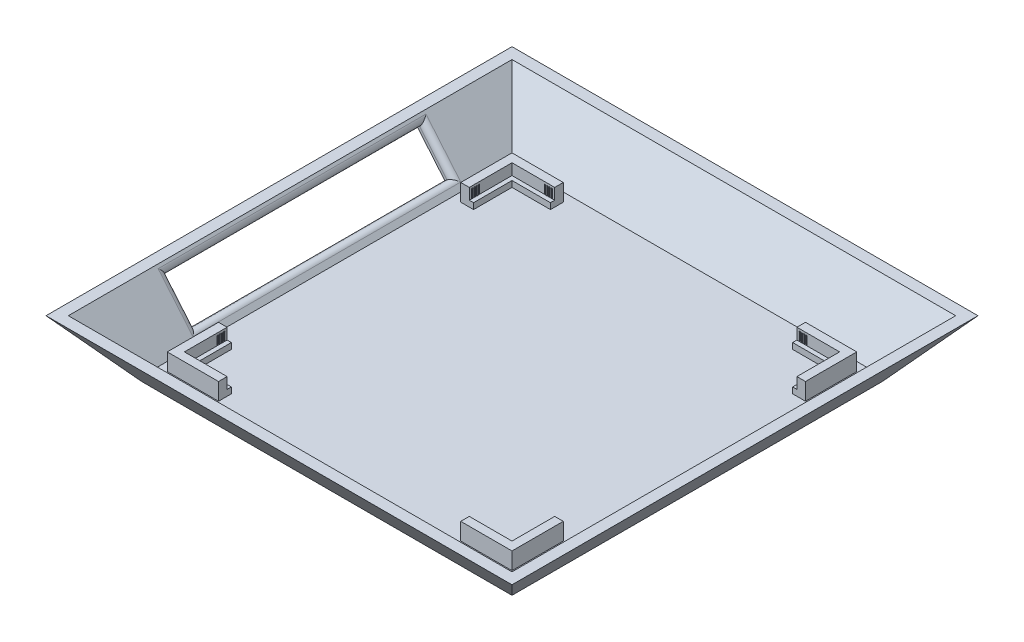
SolidWorks part; units mm, degrees
ref_plane "Front Plane" through (0, 0, 0) normal (0, 0, 1) x (1, 0, 0)
ref_plane "Top Plane" through (0, 0, 0) normal (0, 1, 0) x (1, 0, 0)
ref_plane "Right Plane" through (0, 0, 0) normal (1, 0, 0) x (0, 0, -1)
sketch "Sketch1" plane through (0, 0, 0) normal (0, 1, 0) x (1, 0, 0)
  line L1 (-65, -65) -> (65, -65)
  line L2 (-65, -65) -> (-65, 65)
  line L3 (-65, 65) -> (65, 65)
  line L4 (65, -65) -> (65, 65)
  line L5 (-65, -65) -> (65, 65) construction
  line L6 (-65, 65) -> (65, -65) construction
  point P0 (0, 0)
  dimension "D1" = 130
  dimension "D2" = 130
extrude "Boss-Extrude1" add sketch "Sketch1" along normal blind 20 draft 40 draft outward yes
shell "Shell1" thickness 3 removed face at (0, 20, 0)
sketch "Sketch2" plane through (0, 3, 0) normal (0, 1, 0) x (1, 0, 0)
  line L1 (-57.5, -57.5) -> (57.5, -57.5)
  line L2 (-57.5, -57.5) -> (-57.5, 57.5)
  line L3 (-57.5, 57.5) -> (57.5, 57.5)
  line L4 (57.5, -57.5) -> (57.5, 57.5)
  line L5 (-57.5, -57.5) -> (57.5, 57.5) construction
  line L6 (-57.5, 57.5) -> (57.5, -57.5) construction
  line L7 (57.5, 57.5) -> (42.5, 57.5)
  line L8 (57.5, 57.5) -> (57.5, 42.5)
  line L9 (57.5, 42.5) -> (42.5, 42.5)
  line L10 (42.5, 57.5) -> (42.5, 42.5)
  line L11 (-57.5, 57.5) -> (-42.5, 57.5)
  line L12 (-57.5, 57.5) -> (-57.5, 42.5)
  line L13 (-57.5, 42.5) -> (-42.5, 42.5)
  line L14 (-42.5, 57.5) -> (-42.5, 42.5)
  line L15 (-57.5, -57.5) -> (-42.5, -57.5)
  line L16 (-57.5, -57.5) -> (-57.5, -42.5)
  line L17 (-57.5, -42.5) -> (-42.5, -42.5)
  line L18 (-42.5, -57.5) -> (-42.5, -42.5)
  line L19 (57.5, -57.5) -> (42.5, -57.5)
  line L20 (57.5, -57.5) -> (57.5, -42.5)
  line L21 (57.5, -42.5) -> (42.5, -42.5)
  line L22 (42.5, -57.5) -> (42.5, -42.5)
  line L23 (42.5, -57.5) -> (57.5, -57.5)
  line L24 (42.5, -57.5) -> (42.5, -60.5)
  line L25 (42.5, -60.5) -> (57.5, -60.5)
  line L26 (57.5, -57.5) -> (57.5, -60.5)
  line L27 (57.5, -42.5) -> (60.5, -42.5)
  line L28 (57.5, -42.5) -> (57.5, -60.5)
  line L29 (57.5, -60.5) -> (60.5, -60.5)
  line L30 (60.5, -42.5) -> (60.5, -60.5)
  line L31 (-57.5, -57.5) -> (-42.5, -57.5)
  line L32 (-57.5, -57.5) -> (-57.5, -60.5)
  line L33 (-57.5, -60.5) -> (-42.5, -60.5)
  line L34 (-42.5, -57.5) -> (-42.5, -60.5)
  line L35 (-57.5, -42.5) -> (-60.5, -42.5)
  line L36 (-57.5, -42.5) -> (-57.5, -60.5)
  line L37 (-57.5, -60.5) -> (-60.5, -60.5)
  line L38 (-60.5, -42.5) -> (-60.5, -60.5)
  line L39 (42.5, 57.5) -> (57.5, 57.5)
  line L40 (42.5, 57.5) -> (42.5, 60.5)
  line L41 (42.5, 60.5) -> (57.5, 60.5)
  line L42 (57.5, 57.5) -> (57.5, 60.5)
  line L43 (57.5, 42.5) -> (60.5, 42.5)
  line L44 (57.5, 42.5) -> (57.5, 60.5)
  line L45 (57.5, 60.5) -> (60.5, 60.5)
  line L46 (60.5, 42.5) -> (60.5, 60.5)
  line L47 (-57.5, 57.5) -> (-42.5, 57.5)
  line L48 (-57.5, 57.5) -> (-57.5, 60.5)
  line L49 (-57.5, 60.5) -> (-42.5, 60.5)
  line L50 (-42.5, 57.5) -> (-42.5, 60.5)
  line L51 (-57.5, 42.5) -> (-60.5, 42.5)
  line L52 (-57.5, 42.5) -> (-57.5, 60.5)
  line L53 (-57.5, 60.5) -> (-60.5, 60.5)
  line L54 (-60.5, 42.5) -> (-60.5, 60.5)
  point P0 (0, 0)
  dimension "D1" = 115
  dimension "D2" = 115
  dimension "D3" = 15
  dimension "D4" = 15
  dimension "D5" = 15
  dimension "D6" = 15
  dimension "D7" = 3
  dimension "D8" = 3
  dimension "D9" = 3
  dimension "D10" = 3
  dimension "D11" = 3
  dimension "D12" = 3
  dimension "D13" = 3
  dimension "D14" = 3
extrude "Boss-Extrude2" add sketch "Sketch2" along normal blind 6 contours L54 L51 L2 L48 L53 | L3 L50 L49 L48 | L35 L38 L37 L32 L2 | L3 L42 L41 L40 | L43 L46 L45 L42 L4 | L34 L1 L32 L33 | L26 L1 L24 L25 | L30 L27 L4 L26 L29 region at (-59, 3, 51.5) region at (-50, 3, 59) region at (50, 3, 59) region at (-59, 3, -51.5) region at (59, 3, 51.5) region at (-50, 3, -59) region at (59, 3, -51.5) region at (50, 3, -59)
sketch "Sketch3" plane through (0, 3, 0) normal (0, 1, 0) x (1, 0, 0)
  line L1 (-57.5, -57.5) -> (57.5, -57.5)
  line L2 (-57.5, -57.5) -> (-57.5, 57.5)
  line L3 (-57.5, 57.5) -> (57.5, 57.5)
  line L4 (57.5, -57.5) -> (57.5, 57.5)
  line L5 (-57.5, -57.5) -> (57.5, 57.5) construction
  line L6 (-57.5, 57.5) -> (57.5, -57.5) construction
  line L7 (-57.5, 42.5) -> (-56, 42.5)
  line L8 (-57.5, 42.5) -> (-57.5, 57.5)
  line L9 (-57.5, 57.5) -> (-56, 57.5)
  line L10 (-56, 42.5) -> (-56, 57.5)
  line L11 (-42.5, 57.5) -> (-56, 57.5)
  line L12 (-42.5, 57.5) -> (-42.5, 56)
  line L13 (-42.5, 56) -> (-56, 56)
  line L14 (-56, 57.5) -> (-56, 56)
  line L15 (57.5, 42.5) -> (56, 42.5)
  line L16 (57.5, 42.5) -> (57.5, 57.5)
  line L17 (57.5, 57.5) -> (56, 57.5)
  line L18 (56, 42.5) -> (56, 57.5)
  line L19 (42.5, 57.5) -> (56, 57.5)
  line L20 (42.5, 57.5) -> (42.5, 56)
  line L21 (42.5, 56) -> (56, 56)
  line L22 (56, 57.5) -> (56, 56)
  line L23 (-57.5, -42.5) -> (-56, -42.5)
  line L24 (-57.5, -42.5) -> (-57.5, -57.5)
  line L25 (-57.5, -57.5) -> (-56, -57.5)
  line L26 (-56, -42.5) -> (-56, -57.5)
  line L27 (-42.5, -57.5) -> (-56, -57.5)
  line L28 (-42.5, -57.5) -> (-42.5, -56)
  line L29 (-42.5, -56) -> (-56, -56)
  line L30 (-56, -57.5) -> (-56, -56)
  line L31 (57.5, -42.5) -> (56, -42.5)
  line L32 (57.5, -42.5) -> (57.5, -57.5)
  line L33 (57.5, -57.5) -> (56, -57.5)
  line L34 (56, -42.5) -> (56, -57.5)
  line L35 (42.5, -57.5) -> (56, -57.5)
  line L36 (42.5, -57.5) -> (42.5, -56)
  line L37 (42.5, -56) -> (56, -56)
  line L38 (56, -57.5) -> (56, -56)
  point P0 (0, 0)
  line M10 (-57.5, -42.5) -> (-57.5, -57.5)
  line M11 (-57.5, -57.5) -> (-42.5, -57.5)
  line M24 (-57.5, 57.5) -> (-57.5, 42.5)
  line M25 (57.5, 57.5) -> (42.5, 57.5)
  line M30 (57.5, 42.5) -> (57.5, 57.5)
  line M33 (42.5, -57.5) -> (57.5, -57.5)
  line M34 (57.5, -57.5) -> (57.5, -42.5)
  dimension "D1" = 1.5
  dimension "D2" = 1.5
  dimension "D3" = 1.5
  dimension "D4" = 1.5
extrude "Boss-Extrude3" add sketch "Sketch3" along normal blind 2.1 contours L7 L10 L3 M24 | L20 L21 L18 L3 | L18 L15 M30 M25 | L26 L23 M10 M11 | L28 L29 L26 L1 | L37 L36 L34 M33 | L31 L34 L1 M34 | L11 L12 L13 L14 region at (-56.75, 3, 50) region at (-49.25, 3, 56.75) region at (-56.75, 3, -50) region at (49.25, 3, 56.75) region at (56.75, 3, 50) region at (49.25, 3, -56.75) region at (56.75, 3, -50)
sketch "Sketch4" plane through (0, 0, -57.5) normal (0, 0, 1) x (1, 0, 0)
  line L1 (-43.3, 8.25) -> (-43.7, 8.25)
  line L2 (-43.3, 8.25) -> (-43.3, 5.25)
  line L3 (-43.3, 5.25) -> (-43.7, 5.25)
  line L4 (-43.7, 8.25) -> (-43.7, 5.25)
  line L5 (-44.1, 8.25) -> (-44.5, 8.25)
  line L6 (-44.1, 8.25) -> (-44.1, 5.25)
  line L7 (-44.1, 5.25) -> (-44.5, 5.25)
  line L8 (-44.5, 8.25) -> (-44.5, 5.25)
  line L9 (-44.9, 8.25) -> (-45.3, 8.25)
  line L10 (-44.9, 8.25) -> (-44.9, 5.25)
  line L11 (-44.9, 5.25) -> (-45.3, 5.25)
  line L12 (-45.3, 8.25) -> (-45.3, 5.25)
  line L13 (-45.7, 8.25) -> (-46.1, 8.25)
  line L14 (-45.7, 8.25) -> (-45.7, 5.25)
  line L15 (-45.7, 5.25) -> (-46.1, 5.25)
  line L16 (-46.1, 8.25) -> (-46.1, 5.25)
  line L17 (-57.5, 9) -> (-42.5, 9) construction
  line L18 (-42.5, 9) -> (-42.5, 5.1) construction
  dimension "D1" = 0.4
  dimension "D2" = 0.4
  dimension "D3" = 0.4
  dimension "D4" = 0.4
  dimension "D5" = 3
  dimension "D6" = 3
  dimension "D7" = 3
  dimension "D8" = 3
  dimension "D9" = 0.75
  dimension "D10" = 0.75
  dimension "D11" = 0.75
  dimension "D12" = 0.75
  dimension "D13" = 0.8
  dimension "D14" = 0.4
  dimension "D15" = 0.4
  dimension "D16" = 0.4
extrude "Boss-Extrude4" add sketch "Sketch4" along normal blind 0.2
chamfer "Chamfer2" distance 0.15 angle 45 8 edges at (-43.3, 6.75, -57.3) (-43.7, 6.75, -57.3) (-44.1, 6.75, -57.3) (-44.5, 6.75, -57.3) (-44.9, 6.75, -57.3) (-45.3, 6.75, -57.3) (-45.7, 6.75, -57.3) (-46.1, 6.75, -57.3)
sketch "Sketch5" plane through (-57.5, 0, 0) normal (1, 0, 0) x (0, 0, -1)
  line L0 (42.5, 9) -> (42.5, 5.1) construction
  line L1 (43.3, 8.25) -> (43.7, 8.25)
  line L2 (43.3, 8.25) -> (43.3, 5.25)
  line L3 (43.3, 5.25) -> (43.7, 5.25)
  line L4 (43.7, 8.25) -> (43.7, 5.25)
  line L5 (42.5, 9) -> (57.5, 9) construction
  line L6 (44.1, 8.25) -> (44.1, 5.25)
  line L7 (44.1, 8.25) -> (44.5, 8.25)
  line L8 (44.5, 8.25) -> (44.5, 5.25)
  line L9 (44.1, 5.25) -> (44.5, 5.25)
  line L10 (44.9, 8.25) -> (44.9, 5.25)
  line L11 (44.9, 8.25) -> (45.3, 8.25)
  line L12 (45.3, 8.25) -> (45.3, 5.25)
  line L13 (44.9, 5.25) -> (45.3, 5.25)
  line L14 (45.7, 8.25) -> (45.7, 5.25)
  line L15 (45.7, 8.25) -> (46.1, 8.25)
  line L16 (46.1, 8.25) -> (46.1, 5.25)
  line L17 (45.7, 5.25) -> (46.1, 5.25)
  dimension "D1" = 0.4
  dimension "D2" = 3
  dimension "D3" = 0.8
  dimension "D4" = 0.75
  dimension "D5" = 4
extrude "Boss-Extrude5" add sketch "Sketch5" along normal blind 0.2
chamfer "Chamfer3" distance 0.15 angle 45 8 edges at (-57.3, 6.75, -46.1) (-57.3, 6.75, -45.7) (-57.3, 6.75, -45.3) (-57.3, 6.75, -44.9) (-57.3, 6.75, -44.1) (-57.3, 6.75, -44.5) (-57.3, 6.75, -43.7) (-57.3, 6.75, -43.3)
sketch "Sketch6" plane through (-57.5, 0, 0) normal (1, 0, 0) x (0, 0, -1)
  line L0 (-42.5, 9) -> (-42.5, 5.1) construction
  line L1 (-43.3, 8.25) -> (-43.7, 8.25)
  line L2 (-43.3, 8.25) -> (-43.3, 5.25)
  line L3 (-43.3, 5.25) -> (-43.7, 5.25)
  line L4 (-43.7, 8.25) -> (-43.7, 5.25)
  line L5 (-42.5, 9) -> (-57.5, 9) construction
  line L6 (-44.1, 8.25) -> (-44.1, 5.25)
  line L7 (-44.1, 8.25) -> (-44.5, 8.25)
  line L8 (-44.5, 8.25) -> (-44.5, 5.25)
  line L9 (-44.1, 5.25) -> (-44.5, 5.25)
  line L10 (-44.9, 8.25) -> (-44.9, 5.25)
  line L11 (-44.9, 8.25) -> (-45.3, 8.25)
  line L12 (-45.3, 8.25) -> (-45.3, 5.25)
  line L13 (-44.9, 5.25) -> (-45.3, 5.25)
  line L14 (-45.7, 8.25) -> (-45.7, 5.25)
  line L15 (-45.7, 8.25) -> (-46.1, 8.25)
  line L16 (-46.1, 8.25) -> (-46.1, 5.25)
  line L17 (-45.7, 5.25) -> (-46.1, 5.25)
  dimension "D1" = 0.4
  dimension "D2" = 3
  dimension "D3" = 0.8
  dimension "D4" = 0.75
  dimension "D5" = 4
extrude "Boss-Extrude6" add sketch "Sketch6" along normal blind 0.2
chamfer "Chamfer4" distance 0.15 angle 45 8 edges at (-57.3, 6.75, 44.5) (-57.3, 6.75, 44.1) (-57.3, 6.75, 43.3) (-57.3, 6.75, 43.7) (-57.3, 6.75, 44.9) (-57.3, 6.75, 45.3) (-57.3, 6.75, 45.7) (-57.3, 6.75, 46.1)
sketch "Sketch7" plane through (0, 0, 57.5) normal (0, 0, -1) x (-1, 0, 0)
  line L0 (42.5, 9) -> (42.5, 5.1) construction
  line L1 (43.3, 8.25) -> (43.7, 8.25)
  line L2 (43.3, 8.25) -> (43.3, 5.25)
  line L3 (43.3, 5.25) -> (43.7, 5.25)
  line L4 (43.7, 8.25) -> (43.7, 5.25)
  line L5 (57.5, 9) -> (42.5, 9) construction
  line L6 (44.1, 8.25) -> (44.1, 5.25)
  line L7 (44.1, 8.25) -> (44.5, 8.25)
  line L8 (44.5, 8.25) -> (44.5, 5.25)
  line L9 (44.1, 5.25) -> (44.5, 5.25)
  line L10 (44.9, 8.25) -> (44.9, 5.25)
  line L11 (44.9, 8.25) -> (45.3, 8.25)
  line L12 (45.3, 8.25) -> (45.3, 5.25)
  line L13 (44.9, 5.25) -> (45.3, 5.25)
  line L14 (45.7, 8.25) -> (45.7, 5.25)
  line L15 (45.7, 8.25) -> (46.1, 8.25)
  line L16 (46.1, 8.25) -> (46.1, 5.25)
  line L17 (45.7, 5.25) -> (46.1, 5.25)
  dimension "D1" = 3
  dimension "D2" = 0.4
  dimension "D3" = 0.8
  dimension "D4" = 0.75
  dimension "D5" = 4
extrude "Boss-Extrude7" add sketch "Sketch7" along normal blind 0.2
chamfer "Chamfer5" distance 0.15 angle 45 8 edges at (-46.1, 6.75, 57.3) (-45.7, 6.75, 57.3) (-44.9, 6.75, 57.3) (-45.3, 6.75, 57.3) (-44.5, 6.75, 57.3) (-44.1, 6.75, 57.3) (-43.7, 6.75, 57.3) (-43.3, 6.75, 57.3)
sketch "Sketch8" plane through (57.5, 0, 0) normal (-1, 0, 0) x (0, 0, 1)
  line L0 (57.5, 9) -> (42.5, 9) construction
  line L1 (43.3, 8.25) -> (43.7, 8.25)
  line L2 (43.3, 8.25) -> (43.3, 5.25)
  line L3 (43.3, 5.25) -> (43.7, 5.25)
  line L4 (43.7, 8.25) -> (43.7, 5.25)
  line L5 (42.5, 9) -> (42.5, 5.1) construction
  line L6 (44.1, 8.25) -> (44.1, 5.25)
  line L7 (44.1, 8.25) -> (44.5, 8.25)
  line L8 (44.5, 8.25) -> (44.5, 5.25)
  line L9 (44.1, 5.25) -> (44.5, 5.25)
  line L10 (44.9, 8.25) -> (44.9, 5.25)
  line L11 (44.9, 8.25) -> (45.3, 8.25)
  line L12 (45.3, 8.25) -> (45.3, 5.25)
  line L13 (44.9, 5.25) -> (45.3, 5.25)
  line L14 (45.7, 8.25) -> (45.7, 5.25)
  line L15 (45.7, 8.25) -> (46.1, 8.25)
  line L16 (46.1, 8.25) -> (46.1, 5.25)
  line L17 (45.7, 5.25) -> (46.1, 5.25)
  dimension "D1" = 3
  dimension "D2" = 0.4
  dimension "D3" = 0.75
  dimension "D4" = 0.8
  dimension "D5" = 4
extrude "Boss-Extrude8" add sketch "Sketch8" along normal blind 0.2
chamfer "Chamfer6" distance 0.15 angle 45 8 edges at (57.3, 6.75, 46.1) (57.3, 6.75, 45.7) (57.3, 6.75, 45.3) (57.3, 6.75, 44.9) (57.3, 6.75, 44.5) (57.3, 6.75, 44.1) (57.3, 6.75, 43.7) (57.3, 6.75, 43.3)
sketch "Sketch9" plane through (0, 0, 57.5) normal (0, 0, -1) x (-1, 0, 0)
  line L0 (-42.5, 9) -> (-42.5, 5.1) construction
  line L1 (-43.25, 8.25) -> (-43.65, 8.25)
  line L2 (-43.25, 8.25) -> (-43.25, 5.25)
  line L3 (-43.25, 5.25) -> (-43.65, 5.25)
  line L4 (-43.65, 8.25) -> (-43.65, 5.25)
  line L5 (-42.5, 9) -> (-57.5, 9) construction
  line L6 (-44.05, 8.25) -> (-44.05, 5.25)
  line L7 (-44.05, 8.25) -> (-44.45, 8.25)
  line L8 (-44.45, 8.25) -> (-44.45, 5.25)
  line L9 (-44.05, 5.25) -> (-44.45, 5.25)
  line L10 (-44.85, 8.25) -> (-44.85, 5.25)
  line L11 (-44.85, 8.25) -> (-45.25, 8.25)
  line L12 (-45.25, 8.25) -> (-45.25, 5.25)
  line L13 (-44.85, 5.25) -> (-45.25, 5.25)
  line L14 (-45.65, 8.25) -> (-45.65, 5.25)
  line L15 (-45.65, 8.25) -> (-46.05, 8.25)
  line L16 (-46.05, 8.25) -> (-46.05, 5.25)
  line L17 (-45.65, 5.25) -> (-46.05, 5.25)
  dimension "D1" = 0.4
  dimension "D2" = 3
  dimension "D3" = 0.75
  dimension "D4" = 0.75
  dimension "D5" = 4
extrude "Boss-Extrude9" add sketch "Sketch9" along normal blind 0.2
chamfer "Chamfer7" distance 0.15 angle 45 8 edges at (43.25, 6.75, 57.3) (43.65, 6.75, 57.3) (44.05, 6.75, 57.3) (44.45, 6.75, 57.3) (44.85, 6.75, 57.3) (45.25, 6.75, 57.3) (45.65, 6.75, 57.3) (46.05, 6.75, 57.3)
sketch "Sketch10" plane through (0, 0, -57.5) normal (0, 0, 1) x (1, 0, 0)
  line L0 (42.5, 9) -> (42.5, 5.1) construction
  line L1 (43.3, 8.25) -> (43.7, 8.25)
  line L2 (43.3, 8.25) -> (43.3, 5.25)
  line L3 (43.3, 5.25) -> (43.7, 5.25)
  line L4 (43.7, 8.25) -> (43.7, 5.25)
  line L5 (42.5, 9) -> (57.5, 9) construction
  line L6 (44.1, 8.25) -> (44.1, 5.25)
  line L7 (44.1, 8.25) -> (44.5, 8.25)
  line L8 (44.5, 8.25) -> (44.5, 5.25)
  line L9 (44.1, 5.25) -> (44.5, 5.25)
  line L10 (44.9, 8.25) -> (44.9, 5.25)
  line L11 (44.9, 8.25) -> (45.3, 8.25)
  line L12 (45.3, 8.25) -> (45.3, 5.25)
  line L13 (44.9, 5.25) -> (45.3, 5.25)
  line L14 (45.7, 8.25) -> (45.7, 5.25)
  line L15 (45.7, 8.25) -> (46.1, 8.25)
  line L16 (46.1, 8.25) -> (46.1, 5.25)
  line L17 (45.7, 5.25) -> (46.1, 5.25)
  dimension "D1" = 3
  dimension "D2" = 0.4
  dimension "D3" = 0.8
  dimension "D4" = 0.75
  dimension "D5" = 4
extrude "Boss-Extrude10" add sketch "Sketch10" along normal blind 0.2
chamfer "Chamfer8" distance 0.15 angle 45 8 edges at (46.1, 6.75, -57.3) (45.7, 6.75, -57.3) (45.3, 6.75, -57.3) (44.9, 6.75, -57.3) (44.5, 6.75, -57.3) (44.1, 6.75, -57.3) (43.7, 6.75, -57.3) (43.3, 6.75, -57.3)
sketch "Sketch11" plane through (57.5, 0, 0) normal (-1, 0, 0) x (0, 0, 1)
  line L0 (-42.5, 9) -> (-57.5, 9) construction
  line L1 (-43.7, 8.25) -> (-43.3, 8.25)
  line L2 (-43.7, 8.25) -> (-43.7, 5.25)
  line L3 (-43.7, 5.25) -> (-43.3, 5.25)
  line L4 (-43.3, 8.25) -> (-43.3, 5.25)
  line L5 (-42.5, 9) -> (-42.5, 5.1) construction
  line L6 (-44.5, 8.25) -> (-44.5, 5.25)
  line L7 (-44.5, 8.25) -> (-44.1, 8.25)
  line L8 (-44.1, 8.25) -> (-44.1, 5.25)
  line L9 (-44.5, 5.25) -> (-44.1, 5.25)
  line L10 (-45.3, 8.25) -> (-45.3, 5.25)
  line L11 (-45.3, 8.25) -> (-44.9, 8.25)
  line L12 (-44.9, 8.25) -> (-44.9, 5.25)
  line L13 (-45.3, 5.25) -> (-44.9, 5.25)
  line L14 (-46.1, 8.25) -> (-46.1, 5.25)
  line L15 (-46.1, 8.25) -> (-45.7, 8.25)
  line L16 (-45.7, 8.25) -> (-45.7, 5.25)
  line L17 (-46.1, 5.25) -> (-45.7, 5.25)
  dimension "D1" = 0.4
  dimension "D2" = 3
  dimension "D3" = 0.75
  dimension "D4" = 0.8
  dimension "D5" = 4
extrude "Boss-Extrude11" add sketch "Sketch11" along normal blind 0.2
chamfer "Chamfer9" distance 0.15 angle 45 8 edges at (57.3, 6.75, -43.3) (57.3, 6.75, -43.7) (57.3, 6.75, -44.1) (57.3, 6.75, -44.5) (57.3, 6.75, -44.9) (57.3, 6.75, -45.3) (57.3, 6.75, -45.7) (57.3, 6.75, -46.1)
sketch "Sketch13" plane through (-38.1436, -32.0063, 0) normal (-0.766, -0.6428, 0) x (0, 0, 1)
  line L1 (-45, 47.3343) -> (45, 47.3343)
  line L2 (-45, 47.3343) -> (-45, 62.3343)
  line L3 (-45, 62.3343) -> (45, 62.3343)
  line L4 (45, 47.3343) -> (45, 62.3343)
  line L5 (-45, 47.3343) -> (45, 62.3343) construction
  line L6 (-45, 62.3343) -> (45, 47.3343) construction
  line L7 (-81.782, 67.8893) -> (81.782, 67.8893) construction
  point P0 (0, 54.8343)
  dimension "D1" = 15
  dimension "D2" = 5.555
  dimension "D3" = 90
  dimension "D4" = 20
extrude "Cut-Extrude2" cut sketch "Sketch13" against normal blind 3.2
fillet "Fillet1" radius 2 4 edges at (-71.0923, 11.9277, -45) (-66.2714, 6.1823, 0) (-75.9132, 17.673, 0) (-71.0923, 11.9277, 45)
